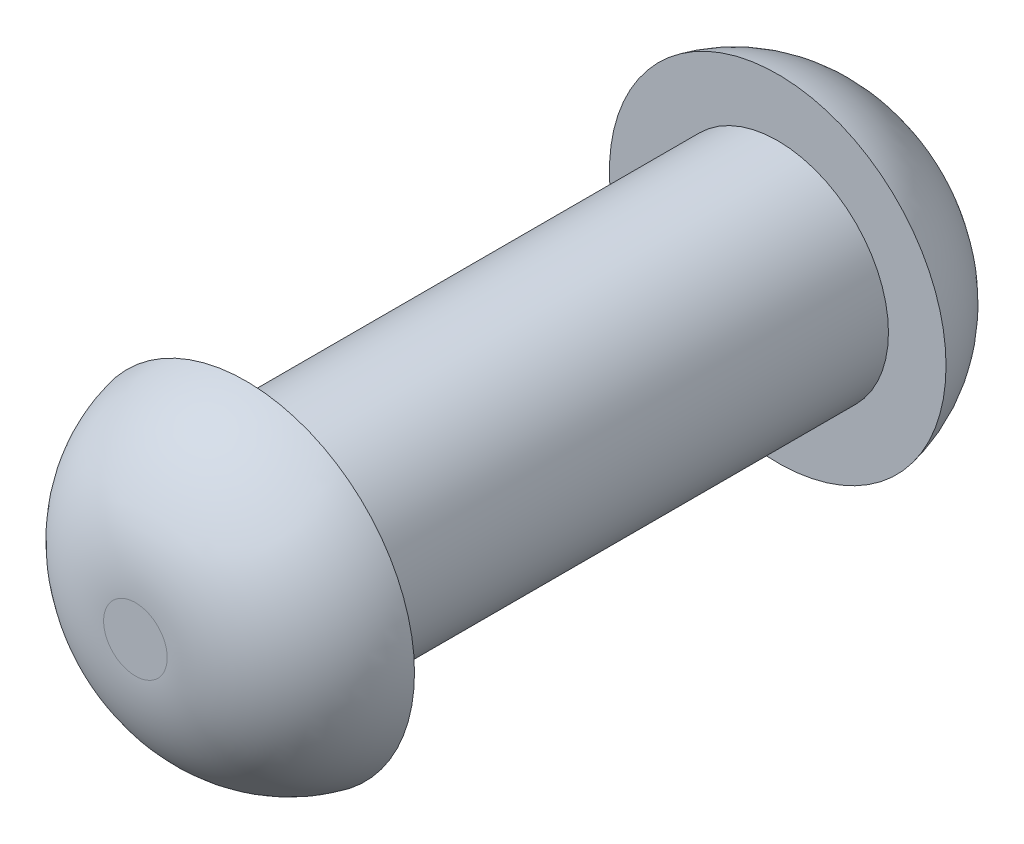
SolidWorks part; units mm, degrees
ref_plane "Alzado" through (0, 0, 0) normal (0, 0, 1) x (1, 0, 0)
ref_plane "Planta" through (0, 0, 0) normal (0, 1, 0) x (1, 0, 0)
ref_plane "Vista lateral" through (0, 0, 0) normal (1, 0, 0) x (0, 0, -1)
sketch "Croquis1" plane through (0, 0, 0) normal (0, 0, 1) x (1, 0, 0)
  circle A0 centre (0, 0) radius 1.5875
  dimension "D1" = 3.175
extrude "Saliente-Extruir1" add sketch "Croquis1" along normal mid plane 7.62
sketch "Croquis2" plane through (0, 0, 3.81) normal (0, 0, 1) x (1, 0, 0)
  circle A0 centre (0, 0) radius 2.413
  dimension "D1" = 4.826
extrude "Saliente-Extruir2" add sketch "Croquis2" along normal blind 1.5875
fillet "Redondeo1" radius 2 1 edges at (2.413, 0, 5.3975)
mirror "Simetría4" about plane through (0, 0, 0) normal (0, 0, 1) of "Saliente-Extruir2"
fillet "Redondeo2" radius 2 1 edges at (2.413, 0, -5.3975)
